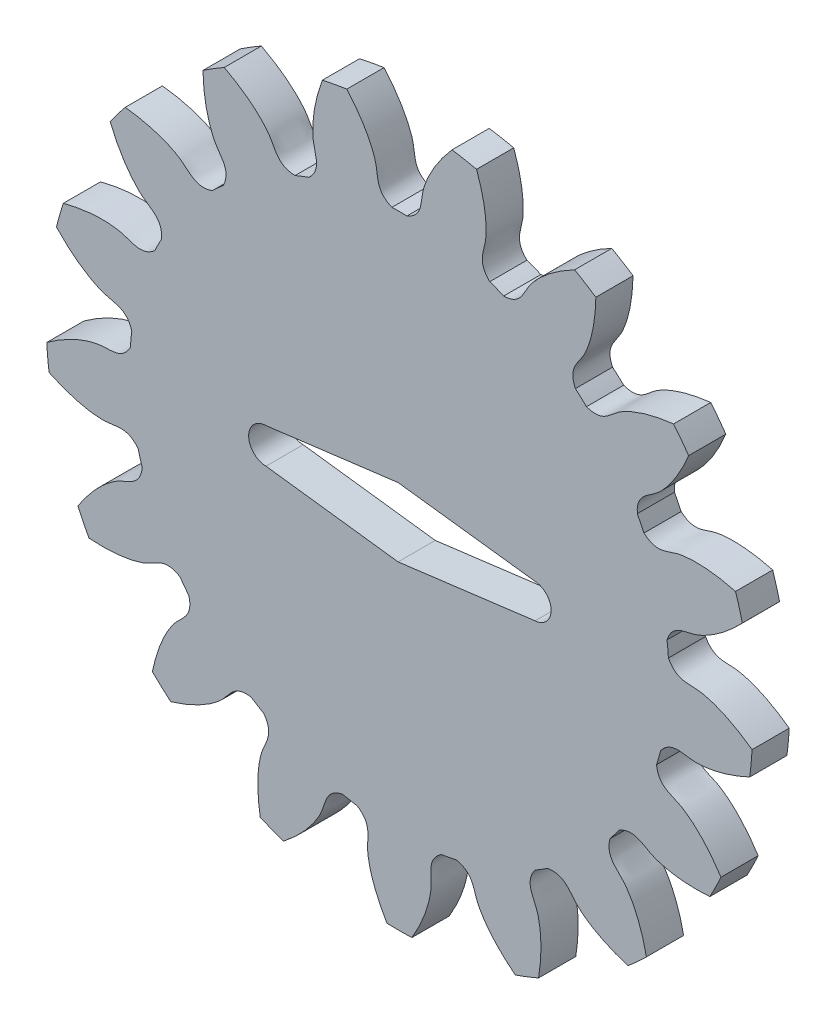
SolidWorks part; units mm, degrees
ref_plane "前视基准面" through (0, 0, 0) normal (0, 0, 1) x (1, 0, 0)
ref_plane "上视基准面" through (0, 0, 0) normal (0, 1, 0) x (1, 0, 0)
ref_plane "右视基准面" through (0, 0, 0) normal (1, 0, 0) x (0, 0, -1)
sketch "草图1" plane through (0, 0, 0) normal (0, 0, 1) x (1, 0, 0)
  circle A0 centre (0, 0) radius 38
extrude "凸台-拉伸1" add sketch "草图1" along normal blind 30
ref_axis "基准轴1" through (0, 0, -0.4001) along (0, 0, 1)
sketch "草图2" plane through (0, 0, 0) normal (0, 0, 1) x (1, 0, 0)
  line L0 (0, 0) -> (0, 38) construction
  circle A0 centre (0, 0) radius 38 construction
  arc A1 (0.8068, 28.9888) -> (-0.8068, 28.9888) centre (0, 0) ccw
  arc A2 (12.4626, 42.9629) -> (-12.4626, 42.9629) centre (0, 0) ccw
  spline S0 degree 3 poles (0.8068, 28.9888) (2.5115, 29.6993) (2.2648, 31.0193) (2.5532, 32.2593) (2.5799, 32.3646) (2.6121, 32.4817) (2.6502, 32.6103) (2.6948, 32.7504) (2.7462, 32.9016) (2.8051, 33.0638) (2.8717, 33.2367) (2.9467, 33.4201) (3.0303, 33.6137) (3.1231, 33.8172) (3.2255, 34.0303) (3.3379, 34.2527) (3.4607, 34.4842) (3.5944, 34.7243) (3.7392, 34.9727) (3.8956, 35.2291) (4.064, 35.4931) (4.2448, 35.7643) (4.4382, 36.0423) (4.6446, 36.3267) (4.8644, 36.6172) (5.0979, 36.9132) (5.3454, 37.2144) (5.6071, 37.5203) (5.8834, 37.8304) (6.1745, 38.1443) (6.4808, 38.4616) (6.8024, 38.7816) (7.1395, 39.104) (7.4925, 39.4282) (7.8614, 39.7538) (8.2465, 40.0802) (8.648, 40.4069) (9.066, 40.7334) (9.5007, 41.0591) (9.9522, 41.3835) (10.4206, 41.706) (10.906, 42.0262) (11.5833, 42.4537) (12.1063, 42.7621) (12.4626, 42.9629) knots 0 0 0 0 0.193883 0.199024 0.204851 0.211363 0.21856 0.226443 0.235011 0.244265 0.254205 0.264829 0.27614 0.288136 0.300817 0.314184 0.328236 0.342973 0.358397 0.374505 0.391299 0.408779 0.426944 0.445795 0.465331 0.485552 0.506459 0.528051 0.550329 0.573293 0.596941 0.621276 0.646296 0.672001 0.698392 0.725468 0.753229 0.781677 0.810809 0.840627 0.871131 0.90232 0.934195 1 1 1 1
  spline S1 degree 3 poles (-0.8068, 28.9888) (-2.5115, 29.6993) (-2.2648, 31.0193) (-2.5532, 32.2593) (-2.5799, 32.3646) (-2.6121, 32.4817) (-2.6502, 32.6103) (-2.6948, 32.7504) (-2.7462, 32.9016) (-2.8051, 33.0638) (-2.8717, 33.2367) (-2.9467, 33.4201) (-3.0303, 33.6137) (-3.1231, 33.8172) (-3.2255, 34.0303) (-3.3379, 34.2527) (-3.4607, 34.4842) (-3.5944, 34.7243) (-3.7392, 34.9727) (-3.8956, 35.2291) (-4.064, 35.4931) (-4.2448, 35.7643) (-4.4382, 36.0423) (-4.6446, 36.3267) (-4.8644, 36.6172) (-5.0979, 36.9132) (-5.3454, 37.2144) (-5.6071, 37.5203) (-5.8834, 37.8304) (-6.1745, 38.1443) (-6.4808, 38.4616) (-6.8024, 38.7816) (-7.1395, 39.104) (-7.4925, 39.4282) (-7.8614, 39.7538) (-8.2465, 40.0802) (-8.648, 40.4069) (-9.066, 40.7334) (-9.5007, 41.0591) (-9.9522, 41.3835) (-10.4206, 41.706) (-10.906, 42.0262) (-11.5833, 42.4537) (-12.1063, 42.7621) (-12.4626, 42.9629) knots 0 0 0 0 0.193883 0.199024 0.204851 0.211363 0.21856 0.226443 0.235011 0.244265 0.254205 0.264829 0.27614 0.288136 0.300817 0.314184 0.328236 0.342973 0.358397 0.374505 0.391299 0.408779 0.426944 0.445795 0.465331 0.485552 0.506459 0.528051 0.550329 0.573293 0.596941 0.621276 0.646296 0.672001 0.698392 0.725468 0.753229 0.781677 0.810809 0.840627 0.871131 0.90232 0.934195 1 1 1 1
extrude "切除-拉伸1" cut sketch "草图2" along normal through all
pattern_circular "阵列(圆周)1" count 17 every 21.176 about axis through (0, 0, -0.4001) along (0, 0, 1) of "切除-拉伸1"
sketch "草图3" plane through (0, 0, 0) normal (0, 0, 1) x (1, 0, 0)
  circle A0 centre (0, 0) radius 34 construction
  dimension "Dn" = 68
sketch "草图4" plane through (0, 0, 30) normal (0, 0, 1) x (1, 0, 0)
  arc A34 (-9.7197, 27.3227) -> (-11.2242, 26.7398) centre (0, 0) ccw
  arc A35 (-18.8502, 32.995) -> (-21.1337, 31.5811) centre (0, 0) ccw
  arc A36 (-18.9334, 21.9665) -> (-20.1258, 20.8794) centre (0, 0) ccw
  arc A37 (-29.4964, 23.9575) -> (-31.115, 21.8142) centre (0, 0) ccw
  arc A38 (-25.5901, 13.6436) -> (-26.3093, 12.1992) centre (0, 0) ccw
  arc A39 (-36.159, 11.6843) -> (-36.894, 9.1011) centre (0, 0) ccw
  arc A40 (-28.7907, 3.4781) -> (-28.9396, 1.8714) centre (0, 0) ccw
  arc A41 (-37.9382, -2.1669) -> (-37.6904, -4.8412) centre (0, 0) ccw
  arc A42 (-28.1029, -7.1572) -> (-27.6614, -8.7091) centre (0, 0) ccw
  arc A43 (-34.5935, -15.7254) -> (-33.3964, -18.1296) centre (0, 0) ccw
  arc A44 (-23.6197, -16.8258) -> (-22.6474, -18.1135) centre (0, 0) ccw
  arc A45 (-26.5768, -27.1601) -> (-24.592, -28.9695) centre (0, 0) ccw
  arc A46 (-15.9466, -24.222) -> (-14.5747, -25.0715) centre (0, 0) ccw
  arc A47 (-14.9708, -34.9267) -> (-12.4664, -35.8969) centre (0, 0) ccw
  arc A48 (-6.1197, -28.3469) -> (-4.5336, -28.6434) centre (0, 0) ccw
  arc A49 (-1.3429, -37.9763) -> (1.3429, -37.9763) centre (0, 0) ccw
  arc A50 (4.5336, -28.6434) -> (6.1197, -28.3469) centre (0, 0) ccw
  arc A51 (12.4664, -35.8969) -> (14.9708, -34.9267) centre (0, 0) ccw
  arc A52 (14.5747, -25.0715) -> (15.9466, -24.222) centre (0, 0) ccw
  arc A53 (24.592, -28.9695) -> (26.5768, -27.1601) centre (0, 0) ccw
  arc A54 (22.6474, -18.1135) -> (23.6197, -16.8258) centre (0, 0) ccw
  arc A55 (33.3964, -18.1296) -> (34.5935, -15.7254) centre (0, 0) ccw
  arc A56 (27.6614, -8.7091) -> (28.1029, -7.1572) centre (0, 0) ccw
  arc A57 (37.6904, -4.8412) -> (37.9382, -2.1669) centre (0, 0) ccw
  arc A58 (28.9396, 1.8714) -> (28.7907, 3.4781) centre (0, 0) ccw
  arc A59 (36.894, 9.1011) -> (36.159, 11.6843) centre (0, 0) ccw
  arc A60 (26.3093, 12.1992) -> (25.5901, 13.6436) centre (0, 0) ccw
  arc A61 (31.115, 21.8142) -> (29.4964, 23.9575) centre (0, 0) ccw
  arc A62 (20.1258, 20.8794) -> (18.9334, 21.9665) centre (0, 0) ccw
  arc A63 (21.1337, 31.5811) -> (18.8502, 32.995) centre (0, 0) ccw
  arc A64 (11.2242, 26.7398) -> (9.7197, 27.3227) centre (0, 0) ccw
  arc A65 (8.2981, 37.0829) -> (5.6581, 37.5764) centre (0, 0) ccw
  arc A66 (0.8068, 28.9888) -> (-0.8068, 28.9888) centre (0, 0) ccw
  arc A67 (-5.6581, 37.5764) -> (-8.2981, 37.0829) centre (0, 0) ccw
  arc A68 (-9.7197, 27.3227) -> (-11.2242, 26.7398) centre (0, 0) ccw
  arc A69 (-18.8502, 32.995) -> (-21.1337, 31.5811) centre (0, 0) ccw
  arc A70 (-18.9334, 21.9665) -> (-20.1258, 20.8794) centre (0, 0) ccw
  arc A71 (-29.4964, 23.9575) -> (-31.115, 21.8142) centre (0, 0) ccw
  arc A72 (-25.5901, 13.6436) -> (-26.3093, 12.1992) centre (0, 0) ccw
  arc A73 (-36.159, 11.6843) -> (-36.894, 9.1011) centre (0, 0) ccw
  arc A74 (-28.7907, 3.4781) -> (-28.9396, 1.8714) centre (0, 0) ccw
  arc A75 (-37.9382, -2.1669) -> (-37.6904, -4.8412) centre (0, 0) ccw
  arc A76 (-28.1029, -7.1572) -> (-27.6614, -8.7091) centre (0, 0) ccw
  arc A77 (-34.5935, -15.7254) -> (-33.3964, -18.1296) centre (0, 0) ccw
  arc A78 (-23.6197, -16.8258) -> (-22.6474, -18.1135) centre (0, 0) ccw
  arc A79 (-26.5768, -27.1601) -> (-24.592, -28.9695) centre (0, 0) ccw
  arc A80 (-15.9466, -24.222) -> (-14.5747, -25.0715) centre (0, 0) ccw
  arc A81 (-14.9708, -34.9267) -> (-12.4664, -35.8969) centre (0, 0) ccw
  arc A82 (-6.1197, -28.3469) -> (-4.5336, -28.6434) centre (0, 0) ccw
  arc A83 (-1.3429, -37.9763) -> (1.3429, -37.9763) centre (0, 0) ccw
  arc A84 (4.5336, -28.6434) -> (6.1197, -28.3469) centre (0, 0) ccw
  arc A85 (12.4664, -35.8969) -> (14.9708, -34.9267) centre (0, 0) ccw
  arc A86 (14.5747, -25.0715) -> (15.9466, -24.222) centre (0, 0) ccw
  arc A87 (24.592, -28.9695) -> (26.5768, -27.1601) centre (0, 0) ccw
  arc A88 (22.6474, -18.1135) -> (23.6197, -16.8258) centre (0, 0) ccw
  arc A89 (33.3964, -18.1296) -> (34.5935, -15.7254) centre (0, 0) ccw
  arc A90 (27.6614, -8.7091) -> (28.1029, -7.1572) centre (0, 0) ccw
  arc A91 (37.6904, -4.8412) -> (37.9382, -2.1669) centre (0, 0) ccw
  arc A92 (28.9396, 1.8714) -> (28.7907, 3.4781) centre (0, 0) ccw
  arc A93 (36.894, 9.1011) -> (36.159, 11.6843) centre (0, 0) ccw
  arc A94 (26.3093, 12.1992) -> (25.5901, 13.6436) centre (0, 0) ccw
  arc A95 (31.115, 21.8142) -> (29.4964, 23.9575) centre (0, 0) ccw
  arc A96 (20.1258, 20.8794) -> (18.9334, 21.9665) centre (0, 0) ccw
  arc A97 (21.1337, 31.5811) -> (18.8502, 32.995) centre (0, 0) ccw
  arc A98 (11.2242, 26.7398) -> (9.7197, 27.3227) centre (0, 0) ccw
  arc A99 (8.2981, 37.0829) -> (5.6581, 37.5764) centre (0, 0) ccw
  arc A100 (0.8068, 28.9888) -> (-0.8068, 28.9888) centre (0, 0) ccw
  arc A101 (-5.6581, 37.5764) -> (-8.2981, 37.0829) centre (0, 0) ccw
  spline S34 degree 3 poles (3206.483, 2402.1157) (-58.0397, -34.3217) (-5.9601, 17.3094) (-14.057, 29.192) (-14.1473, 29.316) (-14.2515, 29.4509) (-14.3436, 29.5654) (-14.4462, 29.6878) (-14.5597, 29.8178) (-14.6843, 29.9549) (-14.8204, 30.0989) (-14.9684, 30.2492) (-15.1284, 30.4054) (-15.3009, 30.5671) (-15.486, 30.7339) (-15.6842, 30.9054) (-15.8955, 31.081) (-16.1203, 31.2603) (-16.3588, 31.4429) (-16.6112, 31.6282) (-16.8777, 31.8158) (-17.2591, 32.0731) (-17.6627, 32.3277) (-18.2038, 32.6472) (-77.0998, 65.046) (-288.9949, -194.6821) (3590.3012, 1755.8862) knots -1.634579 -1.634579 -1.634579 -1.634579 0.661536 0.666677 0.679016 0.686213 0.694096 0.702664 0.711918 0.721858 0.732483 0.743793 0.755789 0.76847 0.781837 0.795889 0.810627 0.82605 0.842158 0.858952 0.876432 0.894597 0.932984 0.953205 0.995704 11.747144 11.747144 11.747144 11.747144 only from (-11.2242, 26.7398) to (-18.8502, 32.995)
  spline S35 degree 3 poles (-3163.825, -2442.2332) (259.4388, 165.7331) (-24.272, 92.345) (-21.0946, 30.5924) (-21.0547, 30.0997) (-21.0017, 29.6255) (-20.9573, 29.2898) (-20.9082, 28.9676) (-20.8548, 28.6591) (-20.7976, 28.3642) (-20.7373, 28.0831) (-20.6743, 27.8156) (-20.6092, 27.5618) (-20.5424, 27.3217) (-20.4745, 27.0952) (-20.406, 26.8823) (-20.3374, 26.6829) (-20.2692, 26.4969) (-20.202, 26.3242) (-20.1362, 26.1647) (-20.0723, 26.0183) (-20.0109, 25.8848) (-19.9366, 25.7314) (-19.8659, 25.5953) (-12.8382, 13.0508) (56.5937, 36.6564) (-3579.505, -1799.594) knots -9.862812 -9.862812 -9.862812 -9.862812 0.025888 0.046795 0.086552 0.105403 0.123568 0.141048 0.157842 0.17395 0.189373 0.204111 0.218163 0.23153 0.244211 0.256207 0.267517 0.278142 0.288082 0.297336 0.305904 0.313787 0.320984 0.333323 0.338464 2.634572 2.634572 2.634572 2.634572 only from (-21.1337, 31.5811) to (-18.9334, 21.9665)
  spline S36 degree 3 poles (2122.2121, 3398.2214) (-41.722, -52.9705) (-11.8105, 13.9875) (-23.6531, 22.1428) (-23.7821, 22.2258) (-23.928, 22.3139) (-24.0553, 22.3874) (-24.1952, 22.4645) (-24.3479, 22.5447) (-24.5137, 22.6276) (-24.6926, 22.7126) (-24.8848, 22.7993) (-25.0905, 22.8872) (-25.3098, 22.9757) (-25.5427, 23.0643) (-25.7894, 23.1526) (-26.0499, 23.24) (-26.3243, 23.326) (-26.6126, 23.4101) (-26.9149, 23.4918) (-27.2311, 23.5704) (-27.6798, 23.6725) (-28.1481, 23.7642) (-28.7681, 23.8666) (-95.3907, 32.802) (-199.1525, -285.9327) (2713.5569, 2934.2815) knots -1.634579 -1.634579 -1.634579 -1.634579 0.661536 0.666677 0.679016 0.686213 0.694096 0.702664 0.711918 0.721858 0.732483 0.743793 0.755789 0.76847 0.781837 0.795889 0.810627 0.82605 0.842158 0.858952 0.876432 0.894597 0.932984 0.953205 0.995704 11.747144 11.747144 11.747144 11.747144 only from (-20.1258, 20.8794) to (-29.4964, 23.9575)
  spline S37 degree 3 poles (-2067.9426, -3420.22) (182.0498, 248.2616) (-55.9918, 77.3411) (-30.7214, 20.9063) (-30.5062, 20.4613) (-30.2855, 20.0383) (-30.1228, 19.7413) (-29.9606, 19.4586) (-29.7993, 19.1902) (-29.6396, 18.9359) (-29.4817, 18.6955) (-29.3264, 18.4688) (-29.1739, 18.2558) (-29.0249, 18.056) (-28.8798, 17.8693) (-28.739, 17.6956) (-28.603, 17.5344) (-28.4723, 17.3856) (-28.3472, 17.2488) (-28.2282, 17.1239) (-28.1158, 17.0104) (-28.0103, 16.908) (-27.8856, 16.7919) (-27.7705, 16.6905) (-16.6857, 7.5318) (39.5302, 54.6251) (-2687.7007, -2971.1378) knots -9.862812 -9.862812 -9.862812 -9.862812 0.025888 0.046795 0.086552 0.105403 0.123568 0.141048 0.157842 0.17395 0.189373 0.204111 0.218163 0.23153 0.244211 0.256207 0.267517 0.278142 0.288082 0.297336 0.305904 0.313787 0.320984 0.333323 0.338464 2.634572 2.634572 2.634572 2.634572 only from (-31.115, 21.8142) to (-25.5901, 13.6436)
  spline S38 degree 3 poles (751.3247, 3935.3785) (-19.7695, -64.4652) (-16.0658, 8.7765) (-30.0548, 12.103) (-30.205, 12.1338) (-30.3729, 12.1633) (-30.5181, 12.1859) (-30.6764, 12.2072) (-30.8479, 12.2268) (-31.0324, 12.2442) (-31.2299, 12.2589) (-31.4405, 12.2703) (-31.664, 12.2779) (-31.9004, 12.2812) (-32.1496, 12.2798) (-32.4115, 12.273) (-32.686, 12.2604) (-32.973, 12.2415) (-33.2722, 12.2157) (-33.5836, 12.1826) (-33.9069, 12.1417) (-34.3621, 12.0749) (-34.8319, 11.9912) (-35.447, 11.8628) (-100.7987, -3.8722) (-82.4133, -338.5665) (1470.3316, 3716.3859) knots -1.634579 -1.634579 -1.634579 -1.634579 0.661536 0.666677 0.679016 0.686213 0.694096 0.702664 0.711918 0.721858 0.732483 0.743793 0.755789 0.76847 0.781837 0.795889 0.810627 0.82605 0.842158 0.858952 0.876432 0.894597 0.932984 0.953205 0.995704 11.747144 11.747144 11.747144 11.747144 only from (-26.3093, 12.1992) to (-36.159, 11.6843)
  spline S39 degree 3 poles (-692.7731, -3936.2872) (80.074, 297.261) (-80.1497, 51.8919) (-36.1991, 8.3967) (-35.8377, 8.0595) (-35.479, 7.7448) (-35.22, 7.5266) (-34.9667, 7.3216) (-34.7193, 7.1296) (-34.4785, 6.9501) (-34.2445, 6.783) (-34.0177, 6.6278) (-33.7986, 6.4841) (-33.5875, 6.3517) (-33.3848, 6.2301) (-33.1907, 6.1189) (-33.0057, 6.0177) (-32.83, 5.9262) (-32.664, 5.8439) (-32.5079, 5.7703) (-32.362, 5.7051) (-32.2267, 5.6478) (-32.0685, 5.5845) (-31.9245, 5.5316) (-18.2797, 0.9956) (17.128, 65.2163) (-1432.9075, -3741.4129) knots -9.862812 -9.862812 -9.862812 -9.862812 0.025888 0.046795 0.086552 0.105403 0.123568 0.141048 0.157842 0.17395 0.189373 0.204111 0.218163 0.23153 0.244211 0.256207 0.267517 0.278142 0.288082 0.297336 0.305904 0.313787 0.320984 0.333323 0.338464 2.634572 2.634572 2.634572 2.634572 only from (-36.894, 9.1011) to (-28.7907, 3.4781)
  spline S40 degree 3 poles (-721.0333, 3941.041) (4.853, -67.2536) (-18.1514, 2.3802) (-32.3974, 0.4287) (-32.5486, 0.4031) (-32.7158, 0.37) (-32.8593, 0.3386) (-33.0147, 0.3013) (-33.1816, 0.2576) (-33.3599, 0.2072) (-33.5494, 0.1495) (-33.7499, 0.0841) (-33.9611, 0.0104) (-34.1827, -0.0719) (-34.4146, -0.1633) (-34.6564, -0.2642) (-34.9078, -0.3751) (-35.1685, -0.4964) (-35.4382, -0.6285) (-35.7166, -0.7718) (-36.0033, -0.9268) (-36.4037, -1.1535) (-36.8115, -1.4013) (-37.3387, -1.7433) (-92.5932, -40.0234) (45.4562, -345.475) (28.5301, 3996.5717) knots -1.634579 -1.634579 -1.634579 -1.634579 0.661536 0.666677 0.679016 0.686213 0.694096 0.702664 0.711918 0.721858 0.732483 0.743793 0.755789 0.76847 0.781837 0.795889 0.810627 0.82605 0.842158 0.858952 0.876432 0.894597 0.932984 0.953205 0.995704 11.747144 11.747144 11.747144 11.747144 only from (-28.9396, 1.8714) to (-37.9382, -2.1669)
  spline S41 degree 3 poles (775.9593, -3920.737) (-32.7163, 306.1137) (-93.4828, 19.4343) (-36.7879, -5.247) (-36.3291, -5.4308) (-35.881, -5.5947) (-35.5606, -5.7046) (-35.2503, -5.8042) (-34.9503, -5.894) (-34.6609, -5.9743) (-34.3823, -6.0456) (-34.1148, -6.1084) (-33.8586, -6.1632) (-33.6139, -6.2104) (-33.3809, -6.2506) (-33.1598, -6.2842) (-32.9507, -6.3117) (-32.7538, -6.3336) (-32.5693, -6.3504) (-32.3972, -6.3626) (-32.2376, -6.3707) (-32.0907, -6.3752) (-31.9203, -6.3771) (-31.767, -6.3744) (-17.405, -5.675) (-7.5875, 66.9998) (15.4078, -4006.3895) knots -9.862812 -9.862812 -9.862812 -9.862812 0.025888 0.046795 0.086552 0.105403 0.123568 0.141048 0.157842 0.17395 0.189373 0.204111 0.218163 0.23153 0.244211 0.256207 0.267517 0.278142 0.288082 0.297336 0.305904 0.313787 0.320984 0.333323 0.338464 2.634572 2.634572 2.634572 2.634572 only from (-37.6904, -4.8412) to (-28.1029, -7.1572)
  spline S42 degree 3 poles (-2096.0117, 3414.444) (28.8201, -60.959) (-17.7855, -4.3375) (-30.3645, -11.3035) (-30.4963, -11.382) (-30.6402, -11.4733) (-30.7627, -11.5545) (-30.8941, -11.6454) (-31.034, -11.7463) (-31.1821, -11.8578) (-31.3379, -11.98) (-31.5012, -12.1135) (-31.6715, -12.2584) (-31.8485, -12.4152) (-32.0317, -12.5842) (-32.2207, -12.7657) (-32.415, -12.9599) (-32.6143, -13.1672) (-32.8181, -13.3878) (-33.026, -13.622) (-33.2373, -13.8701) (-33.5287, -14.2262) (-33.8195, -14.6045) (-34.1876, -15.1138) (-71.8824, -70.7692) (167.1866, -305.7251) (-1417.1247, 3736.9983) knots -1.634579 -1.634579 -1.634579 -1.634579 0.661536 0.666677 0.679016 0.686213 0.694096 0.702664 0.711918 0.721858 0.732483 0.743793 0.755789 0.76847 0.781837 0.795889 0.810627 0.82605 0.842158 0.858952 0.876432 0.894597 0.932984 0.953205 0.995704 11.747144 11.747144 11.747144 11.747144 only from (-27.6614, -8.7091) to (-34.5935, -15.7254)
  spline S43 degree 3 poles (2139.8941, -3375.6695) (-141.0881, 273.624) (-94.1906, -15.6479) (-32.4082, -18.1819) (-31.914, -18.1876) (-31.437, -18.1786) (-31.0985, -18.1654) (-30.7732, -18.1462) (-30.4611, -18.1215) (-30.1622, -18.0918) (-29.8767, -18.0577) (-29.6045, -18.0196) (-29.3458, -17.9782) (-29.1006, -17.9338) (-28.8688, -17.8871) (-28.6505, -17.8385) (-28.4456, -17.7886) (-28.2541, -17.7379) (-28.0759, -17.6869) (-27.911, -17.6361) (-27.7593, -17.5861) (-27.6207, -17.5372) (-27.4612, -17.4774) (-27.3191, -17.4195) (-14.1796, -11.5792) (-31.2782, 59.7345) (1461.6422, -3730.281) knots -9.862812 -9.862812 -9.862812 -9.862812 0.025888 0.046795 0.086552 0.105403 0.123568 0.141048 0.157842 0.17395 0.189373 0.204111 0.218163 0.23153 0.244211 0.256207 0.267517 0.278142 0.288082 0.297336 0.305904 0.313787 0.320984 0.333323 0.338464 2.634572 2.634572 2.634572 2.634572 only from (-33.3964, -18.1296) to (-23.6197, -16.8258)
  spline S44 degree 3 poles (-3187.9122, 2426.7074) (48.8949, -46.4315) (-15.0176, -10.4695) (-24.2307, -21.5092) (-24.3253, -21.6299) (-24.4265, -21.767) (-24.5114, -21.887) (-24.6011, -22.0192) (-24.6951, -22.1639) (-24.7929, -22.3213) (-24.8941, -22.4916) (-24.9981, -22.675) (-25.1046, -22.8717) (-25.2129, -23.0819) (-25.3227, -23.3056) (-25.4334, -23.5431) (-25.5445, -23.7944) (-25.6554, -24.0597) (-25.7658, -24.339) (-25.8749, -24.6325) (-25.9824, -24.9402) (-26.1255, -25.3775) (-26.26, -25.8353) (-26.4192, -26.4432) (-41.4636, -91.9572) (266.3375, -224.6854) (-2671.389, 2972.7227) knots -1.634579 -1.634579 -1.634579 -1.634579 0.661536 0.666677 0.679016 0.686213 0.694096 0.702664 0.711918 0.721858 0.732483 0.743793 0.755789 0.76847 0.781837 0.795889 0.810627 0.82605 0.842158 0.858952 0.876432 0.894597 0.932984 0.953205 0.995704 11.747144 11.747144 11.747144 11.747144 only from (-22.6474, -18.1135) to (-26.5768, -27.1601)
  spline S45 degree 3 poles (3214.8243, -2374.6992) (-230.4051, 204.1799) (-82.1775, -48.6168) (-23.6517, -28.6614) (-23.1888, -28.4881) (-22.7472, -28.3074) (-22.4364, -28.1728) (-22.14, -28.0374) (-21.8579, -27.9016) (-21.5899, -27.7659) (-21.336, -27.631) (-21.096, -27.4972) (-20.8697, -27.3651) (-20.6571, -27.2351) (-20.4578, -27.1078) (-20.2718, -26.9837) (-20.0987, -26.8631) (-19.9385, -26.7467) (-19.7908, -26.6348) (-19.6554, -26.5278) (-19.532, -26.4263) (-19.4204, -26.3307) (-19.2932, -26.2173) (-19.1817, -26.112) (-9.0392, -15.9196) (-50.7447, 44.4018) (2710.4737, -2950.3774) knots -9.862812 -9.862812 -9.862812 -9.862812 0.025888 0.046795 0.086552 0.105403 0.123568 0.141048 0.157842 0.17395 0.189373 0.204111 0.218163 0.23153 0.244211 0.256207 0.267517 0.278142 0.288082 0.297336 0.305904 0.313787 0.320984 0.333323 0.338464 2.634572 2.634572 2.634572 2.634572 only from (-24.592, -28.9695) to (-15.9466, -24.222)
  spline S46 degree 3 poles (-3849.2674, 1111.2306) (62.3661, -25.6332) (-10.2215, -15.1875) (-14.8245, -28.8098) (-14.869, -28.9566) (-14.9139, -29.121) (-14.9497, -29.2636) (-14.9856, -29.4192) (-15.0209, -29.5881) (-15.0553, -29.7702) (-15.0881, -29.9656) (-15.1189, -30.1742) (-15.1471, -30.3961) (-15.1722, -30.6312) (-15.1938, -30.8795) (-15.2112, -31.1409) (-15.224, -31.4154) (-15.2316, -31.7028) (-15.2336, -32.0032) (-15.2294, -32.3162) (-15.2185, -32.642) (-15.1939, -33.1014) (-15.1539, -33.5769) (-15.0828, -34.2013) (-5.4449, -100.726) (329.5181, -113.3007) (-3564.8673, 1806.9643) knots -1.634579 -1.634579 -1.634579 -1.634579 0.661536 0.666677 0.679016 0.686213 0.694096 0.702664 0.711918 0.721858 0.732483 0.743793 0.755789 0.76847 0.781837 0.795889 0.810627 0.82605 0.842158 0.858952 0.876432 0.894597 0.932984 0.953205 0.995704 11.747144 11.747144 11.747144 11.747144 only from (-14.5747, -25.0715) to (-14.9708, -34.9267)
  spline S47 degree 3 poles (3855.5747, -1053.0126) (-288.6047, 107.1602) (-59.0658, -75.0198) (-11.7009, -35.2699) (-11.3318, -34.9412) (-10.9854, -34.6131) (-10.7442, -34.3753) (-10.5167, -34.142) (-10.3026, -33.9134) (-10.1018, -33.6901) (-9.9137, -33.4726) (-9.7383, -33.2611) (-9.575, -33.0562) (-9.4237, -32.8582) (-9.2839, -32.6675) (-9.1552, -32.4845) (-9.0374, -32.3096) (-8.9301, -32.1431) (-8.8328, -31.9854) (-8.7451, -31.8368) (-8.6668, -31.6976) (-8.5972, -31.5681) (-8.5196, -31.4164) (-8.4536, -31.2779) (-2.678, -18.1099) (-63.3577, 23.0723) (3593.2407, -1772.009) knots -9.862812 -9.862812 -9.862812 -9.862812 0.025888 0.046795 0.086552 0.105403 0.123568 0.141048 0.157842 0.17395 0.189373 0.204111 0.218163 0.23153 0.244211 0.256207 0.267517 0.278142 0.288082 0.297336 0.305904 0.313787 0.320984 0.333323 0.338464 2.634572 2.634572 2.634572 2.634572 only from (-12.4664, -35.8969) to (-6.1197, -28.3469)
  spline S48 degree 3 poles (-3990.7577, -354.3241) (67.4145, -1.373) (-4.0449, -17.8544) (-3.4161, -32.2196) (-3.4046, -32.3726) (-3.3871, -32.5421) (-3.369, -32.6879) (-3.3462, -32.846) (-3.3182, -33.0163) (-3.2844, -33.1985) (-3.2444, -33.3925) (-3.1978, -33.5982) (-3.1439, -33.8153) (-3.0824, -34.0436) (-3.0128, -34.2829) (-2.9346, -34.5329) (-2.8474, -34.7935) (-2.7507, -35.0643) (-2.644, -35.3451) (-2.527, -35.6355) (-2.3992, -35.9353) (-2.2103, -36.3548) (-2.0012, -36.7838) (-1.7094, -37.3403) (31.3092, -95.8911) (348.1954, 13.3859) (-3976.8906, 397.1654) knots -1.634579 -1.634579 -1.634579 -1.634579 0.661536 0.666677 0.679016 0.686213 0.694096 0.702664 0.711918 0.721858 0.732483 0.743793 0.755789 0.76847 0.781837 0.795889 0.810627 0.82605 0.842158 0.858952 0.876432 0.894597 0.932984 0.953205 0.995704 11.747144 11.747144 11.747144 11.747144 only from (-4.5336, -28.6434) to (-1.3429, -37.9763)
  spline S49 degree 3 poles (3975.6083, 410.8892) (-307.8266, -4.3321) (-27.9769, -91.2909) (1.8302, -37.115) (2.0556, -36.6752) (2.2601, -36.2441) (2.3992, -35.9353) (2.527, -35.6355) (2.644, -35.3451) (2.7507, -35.0643) (2.8474, -34.7935) (2.9346, -34.5329) (3.0128, -34.2829) (3.0824, -34.0436) (3.1439, -33.8153) (3.1978, -33.5982) (3.2444, -33.3925) (3.2844, -33.1985) (3.3182, -33.0163) (3.3462, -32.846) (3.369, -32.6879) (3.3871, -32.5421) (3.4046, -32.3726) (3.4161, -32.2196) (4.0449, -17.8544) (-67.414, -1.3731) (3990.7206, -354.3209) knots -9.862812 -9.862812 -9.862812 -9.862812 0.025888 0.046795 0.086552 0.105403 0.123568 0.141048 0.157842 0.17395 0.189373 0.204111 0.218163 0.23153 0.244211 0.256207 0.267517 0.278142 0.288082 0.297336 0.305904 0.313787 0.320984 0.333323 0.338464 2.634572 2.634572 2.634572 2.634572 only from (1.3429, -37.9763) to (4.5336, -28.6434)
  spline S50 degree 3 poles (-3593.2741, -1772.0254) (63.3581, 23.0726) (2.678, -18.1099) (8.4536, -31.2779) (8.5196, -31.4164) (8.5972, -31.5681) (8.6668, -31.6976) (8.7451, -31.8368) (8.8328, -31.9854) (8.9301, -32.1431) (9.0374, -32.3096) (9.1552, -32.4845) (9.2839, -32.6675) (9.4237, -32.8582) (9.575, -33.0562) (9.7383, -33.2611) (9.9137, -33.4726) (10.1018, -33.6901) (10.3026, -33.9134) (10.5167, -34.142) (10.7442, -34.3753) (11.0718, -34.6983) (11.4218, -35.0228) (11.8949, -35.4363) (63.8348, -78.1056) (319.847, 138.2646) (-3851.8127, -1066.2729) knots -1.634579 -1.634579 -1.634579 -1.634579 0.661536 0.666677 0.679016 0.686213 0.694096 0.702664 0.711918 0.721858 0.732483 0.743793 0.755789 0.76847 0.781837 0.795889 0.810627 0.82605 0.842158 0.858952 0.876432 0.894597 0.932984 0.953205 0.995704 11.747144 11.747144 11.747144 11.747144 only from (6.1197, -28.3469) to (12.4664, -35.8969)
  spline S51 degree 3 poles (3558.714, 1819.2982) (-285.4748, -115.2394) (6.8904, -95.2326) (15.1141, -33.9476) (15.1654, -33.456) (15.2004, -32.9802) (15.2185, -32.642) (15.2294, -32.3162) (15.2336, -32.0032) (15.2316, -31.7028) (15.224, -31.4154) (15.2112, -31.1409) (15.1938, -30.8795) (15.1722, -30.6312) (15.1471, -30.3961) (15.1189, -30.1742) (15.0881, -29.9656) (15.0553, -29.7702) (15.0209, -29.5881) (14.9856, -29.4192) (14.9497, -29.2636) (14.9139, -29.121) (14.869, -28.9566) (14.8245, -28.8098) (10.2215, -15.1875) (-62.3657, -25.6332) (3849.2316, 1111.2202) knots -9.862812 -9.862812 -9.862812 -9.862812 0.025888 0.046795 0.086552 0.105403 0.123568 0.141048 0.157842 0.17395 0.189373 0.204111 0.218163 0.23153 0.244211 0.256207 0.267517 0.278142 0.288082 0.297336 0.305904 0.313787 0.320984 0.333323 0.338464 2.634572 2.634572 2.634572 2.634572 only from (14.9708, -34.9267) to (14.5747, -25.0715)
  spline S52 degree 3 poles (-2710.4989, -2950.4048) (50.7449, 44.4021) (9.0392, -15.9195) (19.1817, -26.112) (19.2932, -26.2173) (19.4204, -26.3307) (19.532, -26.4263) (19.6554, -26.5278) (19.7908, -26.6348) (19.9385, -26.7467) (20.0987, -26.8631) (20.2718, -26.9837) (20.4578, -27.1078) (20.6571, -27.2351) (20.8697, -27.3651) (21.096, -27.4972) (21.336, -27.631) (21.5899, -27.7659) (21.8579, -27.9016) (22.14, -28.0374) (22.4364, -28.1728) (22.8587, -28.3556) (23.3022, -28.5317) (23.8927, -28.7464) (87.7392, -49.7715) (248.3015, 244.47) (-3206.5263, -2385.7051) knots -1.634579 -1.634579 -1.634579 -1.634579 0.661536 0.666677 0.679016 0.686213 0.694096 0.702664 0.711918 0.721858 0.732483 0.743793 0.755789 0.76847 0.781837 0.795889 0.810627 0.82605 0.842158 0.858952 0.876432 0.894597 0.932984 0.953205 0.995704 11.747144 11.747144 11.747144 11.747144 only from (15.9466, -24.222) to (24.592, -28.9695)
  spline S53 degree 3 poles (2661.1957, 2982.0008) (-224.568, -210.5829) (40.8271, -86.3127) (26.3568, -26.1953) (26.227, -25.7184) (26.0878, -25.2621) (25.9824, -24.9402) (25.8749, -24.6325) (25.7658, -24.339) (25.6554, -24.0597) (25.5445, -23.7944) (25.4334, -23.5431) (25.3227, -23.3056) (25.2129, -23.0819) (25.1046, -22.8717) (24.9981, -22.675) (24.8941, -22.4916) (24.7929, -22.3213) (24.6951, -22.1639) (24.6011, -22.0192) (24.5114, -21.887) (24.4265, -21.767) (24.3253, -21.6299) (24.2307, -21.5092) (15.0176, -10.4695) (-48.8945, -46.4313) (3187.8826, 2426.6848) knots -9.862812 -9.862812 -9.862812 -9.862812 0.025888 0.046795 0.086552 0.105403 0.123568 0.141048 0.157842 0.17395 0.189373 0.204111 0.218163 0.23153 0.244211 0.256207 0.267517 0.278142 0.288082 0.297336 0.305904 0.313787 0.320984 0.333323 0.338464 2.634572 2.634572 2.634572 2.634572 only from (26.5768, -27.1601) to (22.6474, -18.1135)
  spline S54 degree 3 poles (-1461.6558, -3730.3157) (31.2783, 59.7349) (14.1796, -11.5792) (27.3191, -17.4195) (27.4612, -17.4774) (27.6207, -17.5372) (27.7593, -17.5861) (27.911, -17.6361) (28.0759, -17.6869) (28.2541, -17.7379) (28.4456, -17.7886) (28.6505, -17.8385) (28.8688, -17.8871) (29.1006, -17.9338) (29.3458, -17.9782) (29.6045, -18.0196) (29.8767, -18.0577) (30.1622, -18.0918) (30.4611, -18.1215) (30.7732, -18.1462) (31.0985, -18.1654) (31.5583, -18.1833) (32.0355, -18.1873) (32.6637, -18.1742) (99.7939, -14.7155) (143.2215, 317.6583) (-2128.1805, -3382.9346) knots -1.634579 -1.634579 -1.634579 -1.634579 0.661536 0.666677 0.679016 0.686213 0.694096 0.702664 0.711918 0.721858 0.732483 0.743793 0.755789 0.76847 0.781837 0.795889 0.810627 0.82605 0.842158 0.858952 0.876432 0.894597 0.932984 0.953205 0.995704 11.747144 11.747144 11.747144 11.747144 only from (23.6197, -16.8258) to (33.3964, -18.1296)
  spline S55 degree 3 poles (1404.2682, 3741.9677) (-133.3321, -277.486) (69.2498, -65.7358) (34.0398, -14.9053) (33.7465, -14.5074) (33.4518, -14.1322) (33.2373, -13.8701) (33.026, -13.622) (32.8181, -13.3878) (32.6143, -13.1672) (32.415, -12.9599) (32.2207, -12.7657) (32.0317, -12.5842) (31.8485, -12.4152) (31.6715, -12.2584) (31.5012, -12.1135) (31.3379, -11.98) (31.1821, -11.8578) (31.034, -11.7463) (30.8941, -11.6454) (30.7627, -11.5545) (30.6402, -11.4733) (30.4963, -11.382) (30.3645, -11.3035) (17.7856, -4.3376) (-28.8198, -60.9586) (2095.9923, 3414.4122) knots -9.862812 -9.862812 -9.862812 -9.862812 0.025888 0.046795 0.086552 0.105403 0.123568 0.141048 0.157842 0.17395 0.189373 0.204111 0.218163 0.23153 0.244211 0.256207 0.267517 0.278142 0.288082 0.297336 0.305904 0.313787 0.320984 0.333323 0.338464 2.634572 2.634572 2.634572 2.634572 only from (34.5935, -15.7254) to (27.6614, -8.7091)
  spline S56 degree 3 poles (-15.408, -4006.4268) (7.5874, 67.0002) (17.405, -5.675) (31.767, -6.3744) (31.9203, -6.3771) (32.0907, -6.3752) (32.2376, -6.3707) (32.3972, -6.3626) (32.5693, -6.3504) (32.7538, -6.3336) (32.9507, -6.3117) (33.1598, -6.2842) (33.3809, -6.2506) (33.6139, -6.2104) (33.8586, -6.1632) (34.1148, -6.1084) (34.3823, -6.0456) (34.6609, -5.9743) (34.9503, -5.894) (35.2503, -5.8042) (35.5606, -5.7046) (35.9958, -5.5553) (36.4422, -5.3866) (37.0233, -5.1474) (98.3709, 22.3279) (18.7987, 347.9451) (-762.4124, -3923.2801) knots -1.634579 -1.634579 -1.634579 -1.634579 0.661536 0.666677 0.679016 0.686213 0.694096 0.702664 0.711918 0.721858 0.732483 0.743793 0.755789 0.76847 0.781837 0.795889 0.810627 0.82605 0.842158 0.858952 0.876432 0.894597 0.932984 0.953205 0.995704 11.747144 11.747144 11.747144 11.747144 only from (28.1029, -7.1572) to (37.6904, -4.8412)
  spline S57 degree 3 poles (-42.3136, 3996.5611) (-24.089, -306.9131) (88.3201, -36.2808) (37.1256, -1.6021) (36.7084, -1.3371) (36.298, -1.0937) (36.0033, -0.9268) (35.7166, -0.7718) (35.4382, -0.6285) (35.1685, -0.4964) (34.9078, -0.3751) (34.6564, -0.2642) (34.4146, -0.1633) (34.1827, -0.0719) (33.9611, 0.0104) (33.7499, 0.0841) (33.5494, 0.1495) (33.3599, 0.2072) (33.1816, 0.2576) (33.0147, 0.3013) (32.8593, 0.3386) (32.7158, 0.37) (32.5486, 0.4031) (32.3974, 0.4287) (18.1514, 2.3802) (-4.8529, -67.2531) (721.0267, 3941.0043) knots -9.862812 -9.862812 -9.862812 -9.862812 0.025888 0.046795 0.086552 0.105403 0.123568 0.141048 0.157842 0.17395 0.189373 0.204111 0.218163 0.23153 0.244211 0.256207 0.267517 0.278142 0.288082 0.297336 0.305904 0.313787 0.320984 0.333323 0.338464 2.634572 2.634572 2.634572 2.634572 only from (37.9382, -2.1669) to (28.9396, 1.8714)
  spline S58 degree 3 poles (1432.9207, -3741.4477) (-17.1282, 65.2167) (18.2797, 0.9956) (31.9245, 5.5316) (32.0685, 5.5845) (32.2267, 5.6478) (32.362, 5.7051) (32.5079, 5.7703) (32.664, 5.8439) (32.83, 5.9262) (33.0057, 6.0177) (33.1907, 6.1189) (33.3848, 6.2301) (33.5875, 6.3517) (33.7986, 6.4841) (34.0177, 6.6278) (34.2445, 6.783) (34.4785, 6.9501) (34.7193, 7.1296) (34.9667, 7.3216) (35.22, 7.5266) (35.5719, 7.823) (35.9272, 8.1415) (36.3826, 8.5745) (83.6623, 56.3558) (-108.1631, 331.24) (706.3238, -3933.7648) knots -1.634579 -1.634579 -1.634579 -1.634579 0.661536 0.666677 0.679016 0.686213 0.694096 0.702664 0.711918 0.721858 0.732483 0.743793 0.755789 0.76847 0.781837 0.795889 0.810627 0.82605 0.842158 0.858952 0.876432 0.894597 0.932984 0.953205 0.995704 11.747144 11.747144 11.747144 11.747144 only from (28.7907, 3.4781) to (36.894, 9.1011)
  spline S59 degree 3 poles (-1483.1807, 3711.3968) (88.4075, -294.8899) (95.4621, -1.926) (35.1973, 11.9174) (34.7126, 12.0138) (34.242, 12.0925) (33.9069, 12.1417) (33.5836, 12.1826) (33.2722, 12.2157) (32.973, 12.2415) (32.686, 12.2604) (32.4115, 12.273) (32.1496, 12.2798) (31.9004, 12.2812) (31.664, 12.2779) (31.4405, 12.2703) (31.2299, 12.2589) (31.0324, 12.2442) (30.8479, 12.2268) (30.6764, 12.2072) (30.5181, 12.1859) (30.3729, 12.1633) (30.205, 12.1338) (30.0548, 12.103) (16.0659, 8.7766) (19.7695, -64.4648) (-751.3176, 3935.342) knots -9.862812 -9.862812 -9.862812 -9.862812 0.025888 0.046795 0.086552 0.105403 0.123568 0.141048 0.157842 0.17395 0.189373 0.204111 0.218163 0.23153 0.244211 0.256207 0.267517 0.278142 0.288082 0.297336 0.305904 0.313787 0.320984 0.333323 0.338464 2.634572 2.634572 2.634572 2.634572 only from (36.159, 11.6843) to (26.3093, 12.1992)
  spline S60 degree 3 poles (2687.7256, -2971.1654) (-39.5306, 54.6253) (16.6857, 7.5318) (27.7705, 16.6905) (27.8856, 16.7919) (28.0103, 16.908) (28.1158, 17.0104) (28.2282, 17.1239) (28.3472, 17.2488) (28.4723, 17.3856) (28.603, 17.5344) (28.739, 17.6956) (28.8798, 17.8693) (29.0249, 18.056) (29.1739, 18.2558) (29.3264, 18.4688) (29.4817, 18.6955) (29.6396, 18.9359) (29.7993, 19.1902) (29.9606, 19.4586) (30.1228, 19.7413) (30.3438, 20.1448) (30.5601, 20.5702) (30.8283, 21.1384) (57.6547, 82.7726) (-220.5167, 269.7991) (2079.6672, -3412.9729) knots -1.634579 -1.634579 -1.634579 -1.634579 0.661536 0.666677 0.679016 0.686213 0.694096 0.702664 0.711918 0.721858 0.732483 0.743793 0.755789 0.76847 0.781837 0.795889 0.810627 0.82605 0.842158 0.858952 0.876432 0.894597 0.932984 0.953205 0.995704 11.747144 11.747144 11.747144 11.747144 only from (25.5901, 13.6436) to (31.115, 21.8142)
  spline S61 degree 3 poles (-2723.736, 2924.9878) (188.9641, -243.0402) (89.7115, 32.689) (28.5155, 23.8274) (28.0286, 23.7421) (27.5614, 23.6456) (27.2311, 23.5704) (26.9149, 23.4918) (26.6126, 23.4101) (26.3243, 23.326) (26.0499, 23.24) (25.7894, 23.1526) (25.5427, 23.0643) (25.3098, 22.9757) (25.0905, 22.8872) (24.8848, 22.7993) (24.6926, 22.7126) (24.5137, 22.6276) (24.3479, 22.5447) (24.1952, 22.4645) (24.0553, 22.3874) (23.928, 22.3139) (23.7821, 22.2258) (23.6531, 22.1428) (11.8105, 13.9876) (41.7218, -52.97) (-2122.1923, 3398.1899) knots -9.862812 -9.862812 -9.862812 -9.862812 0.025888 0.046795 0.086552 0.105403 0.123568 0.141048 0.157842 0.17395 0.189373 0.204111 0.218163 0.23153 0.244211 0.256207 0.267517 0.278142 0.288082 0.297336 0.305904 0.313787 0.320984 0.333323 0.338464 2.634572 2.634572 2.634572 2.634572 only from (29.4964, 23.9575) to (20.1258, 20.8794)
  spline S62 degree 3 poles (3579.5382, -1799.6108) (-56.5941, 36.6565) (12.8381, 13.0507) (19.8659, 25.5953) (19.9366, 25.7314) (20.0109, 25.8848) (20.0723, 26.0183) (20.1362, 26.1647) (20.202, 26.3242) (20.2692, 26.4969) (20.3374, 26.6829) (20.406, 26.8823) (20.4745, 27.0952) (20.5424, 27.3217) (20.6092, 27.5618) (20.6743, 27.8156) (20.7373, 28.0831) (20.7976, 28.3642) (20.8548, 28.6591) (20.9082, 28.9676) (20.9573, 29.2898) (21.0176, 29.7459) (21.0656, 30.2207) (21.1105, 30.8475) (23.8605, 98.0104) (-303.0884, 171.9204) (3172.1399, -2431.24) knots -1.634579 -1.634579 -1.634579 -1.634579 0.661536 0.666677 0.679016 0.686213 0.694096 0.702664 0.711918 0.721858 0.732483 0.743793 0.755789 0.76847 0.781837 0.795889 0.810627 0.82605 0.842158 0.858952 0.876432 0.894597 0.932984 0.953205 0.995704 11.747144 11.747144 11.747144 11.747144 only from (18.9334, 21.9665) to (21.1337, 31.5811)
  spline S63 degree 3 poles (-3596.4356, 1743.543) (264, -158.3665) (71.8449, 62.8891) (17.9825, 32.5193) (17.5593, 32.264) (17.1585, 32.0052) (16.8777, 31.8158) (16.6112, 31.6282) (16.3588, 31.4429) (16.1203, 31.2603) (15.8955, 31.081) (15.6842, 30.9054) (15.486, 30.7339) (15.3009, 30.5671) (15.1284, 30.4054) (14.9684, 30.2492) (14.8204, 30.0989) (14.6843, 29.9549) (14.5597, 29.8178) (14.4462, 29.6878) (14.3436, 29.5654) (14.2515, 29.4509) (14.1473, 29.316) (14.057, 29.192) (5.9601, 17.3095) (58.0394, -34.3214) (-3206.4532, 2402.0934) knots -9.862812 -9.862812 -9.862812 -9.862812 0.025888 0.046795 0.086552 0.105403 0.123568 0.141048 0.157842 0.17395 0.189373 0.204111 0.218163 0.23153 0.244211 0.256207 0.267517 0.278142 0.288082 0.297336 0.305904 0.313787 0.320984 0.333323 0.338464 2.634572 2.634572 2.634572 2.634572 only from (18.8502, 32.995) to (11.2242, 26.7398)
  spline S64 degree 3 poles (3987.9144, -385.0087) (-66.0143, 13.737) (7.2567, 16.8071) (9.2783, 31.0433) (9.2951, 31.1958) (9.309, 31.3656) (9.318, 31.5123) (9.3247, 31.6719) (9.3284, 31.8444) (9.3287, 32.0297) (9.325, 32.2278) (9.317, 32.4385) (9.3039, 32.6618) (9.2854, 32.8975) (9.261, 33.1455) (9.2301, 33.4057) (9.1922, 33.6778) (9.1469, 33.9618) (9.0936, 34.2574) (9.032, 34.5644) (8.9614, 34.8826) (8.8528, 35.3297) (8.7261, 35.7897) (8.5415, 36.3904) (-13.1562, 100.0114) (-344.7263, 50.8228) (3836.1975, -1121.1546) knots -1.634579 -1.634579 -1.634579 -1.634579 0.661536 0.666677 0.679016 0.686213 0.694096 0.702664 0.711918 0.721858 0.732483 0.743793 0.755789 0.76847 0.781837 0.795889 0.810627 0.82605 0.842158 0.858952 0.876432 0.894597 0.932984 0.953205 0.995704 11.747144 11.747144 11.747144 11.747144 only from (9.7197, 27.3227) to (8.2981, 37.0829)
  spline S65 degree 3 poles (-3983.4167, 326.623) (303.3813, -52.3046) (44.2752, 84.5957) (5.0208, 36.8194) (4.7184, 36.4284) (4.4382, 36.0423) (4.2448, 35.7643) (4.064, 35.4931) (3.8956, 35.2291) (3.7392, 34.9727) (3.5944, 34.7243) (3.4607, 34.4842) (3.3379, 34.2527) (3.2255, 34.0303) (3.1231, 33.8172) (3.0303, 33.6137) (2.9467, 33.4201) (2.8717, 33.2367) (2.8051, 33.0638) (2.7462, 32.9016) (2.6948, 32.7504) (2.6502, 32.6103) (2.6018, 32.447) (2.5624, 32.2987) (-0.6953, 18.2936) (66.5185, -11.0375) (-3857.6647, 1081.5809) knots -9.862812 -9.862812 -9.862812 -9.862812 0.025888 0.046795 0.086552 0.105403 0.123568 0.141048 0.157842 0.17395 0.189373 0.204111 0.218163 0.23153 0.244211 0.256207 0.267517 0.278142 0.288082 0.297336 0.305904 0.313787 0.320984 0.333323 0.338464 2.634572 2.634572 2.634572 2.634572 only from (5.6581, 37.5764) to (0.8068, 28.9888)
  spline S66 degree 3 poles (3857.7006, 1081.5909) (-66.5189, -11.0377) (0.6953, 18.2936) (-2.5624, 32.2987) (-2.6018, 32.447) (-2.6502, 32.6103) (-2.6948, 32.7504) (-2.7462, 32.9016) (-2.8051, 33.0638) (-2.8717, 33.2367) (-2.9467, 33.4201) (-3.0303, 33.6137) (-3.1231, 33.8172) (-3.2255, 34.0303) (-3.3379, 34.2527) (-3.4607, 34.4842) (-3.5944, 34.7243) (-3.7392, 34.9727) (-3.8956, 35.2291) (-4.064, 35.4931) (-4.2448, 35.7643) (-4.5075, 36.1419) (-4.7919, 36.5252) (-5.181, 37.0186) (-48.3961, 88.5053) (-339.8071, -77.1387) (3982.1554, 340.3488) knots -1.634579 -1.634579 -1.634579 -1.634579 0.661536 0.666677 0.679016 0.686213 0.694096 0.702664 0.711918 0.721858 0.732483 0.743793 0.755789 0.76847 0.781837 0.795889 0.810627 0.82605 0.842158 0.858952 0.876432 0.894597 0.932984 0.953205 0.995704 11.747144 11.747144 11.747144 11.747144 only from (-0.8068, 28.9888) to (-5.6581, 37.5764)
  spline S67 degree 3 poles (-3832.4153, -1134.4092) (301.7892, 60.8214) (10.7259, 94.8772) (-8.6189, 36.1468) (-8.7597, 35.673) (-8.8815, 35.2117) (-8.9614, 34.8826) (-9.032, 34.5644) (-9.0936, 34.2574) (-9.1469, 33.9618) (-9.1922, 33.6778) (-9.2301, 33.4057) (-9.261, 33.1455) (-9.2854, 32.8975) (-9.3039, 32.6618) (-9.317, 32.4385) (-9.325, 32.2278) (-9.3287, 32.0297) (-9.3284, 31.8444) (-9.3247, 31.6719) (-9.318, 31.5123) (-9.309, 31.3656) (-9.2951, 31.1958) (-9.2783, 31.0433) (-7.2567, 16.8071) (66.0139, 13.7371) (-3987.8773, -385.0051) knots -9.862812 -9.862812 -9.862812 -9.862812 0.025888 0.046795 0.086552 0.105403 0.123568 0.141048 0.157842 0.17395 0.189373 0.204111 0.218163 0.23153 0.244211 0.256207 0.267517 0.278142 0.288082 0.297336 0.305904 0.313787 0.320984 0.333323 0.338464 2.634572 2.634572 2.634572 2.634572 only from (-8.2981, 37.0829) to (-9.7197, 27.3227)
  spline S68 degree 3 poles (-11.2242, 26.7398) (-13.0705, 26.7865) (-13.3173, 28.1065) (-14.057, 29.192) (-14.1473, 29.316) (-14.2515, 29.4509) (-14.3436, 29.5654) (-14.4462, 29.6878) (-14.5597, 29.8178) (-14.6843, 29.9549) (-14.8204, 30.0989) (-14.9684, 30.2492) (-15.1284, 30.4054) (-15.3009, 30.5671) (-15.486, 30.7339) (-15.6842, 30.9054) (-15.8955, 31.081) (-16.1203, 31.2603) (-16.3588, 31.4429) (-16.6112, 31.6282) (-16.8777, 31.8158) (-17.2591, 32.0731) (-17.6627, 32.3277) (-18.2038, 32.6472) (-18.5688, 32.848) (-18.8265, 32.9827) (-18.8502, 32.995) knots 0.467653 0.467653 0.467653 0.467653 0.661536 0.666677 0.679016 0.686213 0.694096 0.702664 0.711918 0.721858 0.732483 0.743793 0.755789 0.76847 0.781837 0.795889 0.810627 0.82605 0.842158 0.858952 0.876432 0.894597 0.932984 0.953205 0.995704 1 1 1 1
  spline S69 degree 3 poles (-21.1337, 31.5811) (-21.1308, 31.4203) (-21.1223, 31.1296) (-21.0946, 30.5924) (-21.0547, 30.0997) (-21.0017, 29.6255) (-20.9573, 29.2898) (-20.9082, 28.9676) (-20.8548, 28.6591) (-20.7976, 28.3642) (-20.7373, 28.0831) (-20.6743, 27.8156) (-20.6092, 27.5618) (-20.5424, 27.3217) (-20.4745, 27.0952) (-20.406, 26.8823) (-20.3374, 26.6829) (-20.2692, 26.4969) (-20.202, 26.3242) (-20.1362, 26.1647) (-20.0723, 26.0183) (-20.0109, 25.8848) (-19.9366, 25.7314) (-19.8659, 25.5953) (-19.2238, 24.4493) (-18.1522, 23.64) (-18.9334, 21.9665) knots 0 0 0 0 0.025888 0.046795 0.086552 0.105403 0.123568 0.141048 0.157842 0.17395 0.189373 0.204111 0.218163 0.23153 0.244211 0.256207 0.267517 0.278142 0.288082 0.297336 0.305904 0.313787 0.320984 0.333323 0.338464 0.532347 0.532347 0.532347 0.532347
  spline S70 degree 3 poles (-20.1258, 20.8794) (-21.8643, 20.256) (-22.5712, 21.3977) (-23.6531, 22.1428) (-23.7821, 22.2258) (-23.928, 22.3139) (-24.0553, 22.3874) (-24.1952, 22.4645) (-24.3479, 22.5447) (-24.5137, 22.6276) (-24.6926, 22.7126) (-24.8848, 22.7993) (-25.0905, 22.8872) (-25.3098, 22.9757) (-25.5427, 23.0643) (-25.7894, 23.1526) (-26.0499, 23.24) (-26.3243, 23.326) (-26.6126, 23.4101) (-26.9149, 23.4918) (-27.2311, 23.5704) (-27.6798, 23.6725) (-28.1481, 23.7642) (-28.7681, 23.8666) (-29.1809, 23.922) (-29.4699, 23.9545) (-29.4964, 23.9575) knots 0.467653 0.467653 0.467653 0.467653 0.661536 0.666677 0.679016 0.686213 0.694096 0.702664 0.711918 0.721858 0.732483 0.743793 0.755789 0.76847 0.781837 0.795889 0.810627 0.82605 0.842158 0.858952 0.876432 0.894597 0.932984 0.953205 0.995704 1 1 1 1
  spline S71 degree 3 poles (-31.115, 21.8142) (-31.0542, 21.6652) (-30.9412, 21.3972) (-30.7214, 20.9063) (-30.5062, 20.4613) (-30.2855, 20.0383) (-30.1228, 19.7413) (-29.9606, 19.4586) (-29.7993, 19.1902) (-29.6396, 18.9359) (-29.4817, 18.6955) (-29.3264, 18.4688) (-29.1739, 18.2558) (-29.0249, 18.056) (-28.8798, 17.8693) (-28.739, 17.6956) (-28.603, 17.5344) (-28.4723, 17.3856) (-28.3472, 17.2488) (-28.2282, 17.1239) (-28.1158, 17.0104) (-28.0103, 16.908) (-27.8856, 16.7919) (-27.7705, 16.6905) (-26.7578, 15.8538) (-25.4662, 15.4863) (-25.5901, 13.6436) knots 0 0 0 0 0.025888 0.046795 0.086552 0.105403 0.123568 0.141048 0.157842 0.17395 0.189373 0.204111 0.218163 0.23153 0.244211 0.256207 0.267517 0.278142 0.288082 0.297336 0.305904 0.313787 0.320984 0.333323 0.338464 0.532347 0.532347 0.532347 0.532347
  spline S72 degree 3 poles (-26.3093, 12.1992) (-27.7052, 10.9899) (-28.7768, 11.7991) (-30.0548, 12.103) (-30.205, 12.1338) (-30.3729, 12.1633) (-30.5181, 12.1859) (-30.6764, 12.2072) (-30.8479, 12.2268) (-31.0324, 12.2442) (-31.2299, 12.2589) (-31.4405, 12.2703) (-31.664, 12.2779) (-31.9004, 12.2812) (-32.1496, 12.2798) (-32.4115, 12.273) (-32.686, 12.2604) (-32.973, 12.2415) (-33.2722, 12.2157) (-33.5836, 12.1826) (-33.9069, 12.1417) (-34.3621, 12.0749) (-34.8319, 11.9912) (-35.447, 11.8628) (-35.852, 11.7653) (-36.1332, 11.6912) (-36.159, 11.6843) knots 0.467653 0.467653 0.467653 0.467653 0.661536 0.666677 0.679016 0.686213 0.694096 0.702664 0.711918 0.721858 0.732483 0.743793 0.755789 0.76847 0.781837 0.795889 0.810627 0.82605 0.842158 0.858952 0.876432 0.894597 0.932984 0.953205 0.995704 1 1 1 1
  spline S73 degree 3 poles (-36.894, 9.1011) (-36.7836, 8.9841) (-36.5814, 8.775) (-36.1991, 8.3967) (-35.8377, 8.0595) (-35.479, 7.7448) (-35.22, 7.5266) (-34.9667, 7.3216) (-34.7193, 7.1296) (-34.4785, 6.9501) (-34.2445, 6.783) (-34.0177, 6.6278) (-33.7986, 6.4841) (-33.5875, 6.3517) (-33.3848, 6.2301) (-33.1907, 6.1189) (-33.0057, 6.0177) (-32.83, 5.9262) (-32.664, 5.8439) (-32.5079, 5.7703) (-32.362, 5.7051) (-32.2267, 5.6478) (-32.0685, 5.5845) (-31.9245, 5.5316) (-30.678, 5.1172) (-29.3409, 5.2411) (-28.7907, 3.4781) knots 0 0 0 0 0.025888 0.046795 0.086552 0.105403 0.123568 0.141048 0.157842 0.17395 0.189373 0.204111 0.218163 0.23153 0.244211 0.256207 0.267517 0.278142 0.288082 0.297336 0.305904 0.313787 0.320984 0.333323 0.338464 0.532347 0.532347 0.532347 0.532347
  spline S74 degree 3 poles (-28.9396, 1.8714) (-29.8043, 0.2395) (-31.0959, 0.607) (-32.3974, 0.4287) (-32.5486, 0.4031) (-32.7158, 0.37) (-32.8593, 0.3386) (-33.0147, 0.3013) (-33.1816, 0.2576) (-33.3599, 0.2072) (-33.5494, 0.1495) (-33.7499, 0.0841) (-33.9611, 0.0104) (-34.1827, -0.0719) (-34.4146, -0.1633) (-34.6564, -0.2642) (-34.9078, -0.3751) (-35.1685, -0.4964) (-35.4382, -0.6285) (-35.7166, -0.7718) (-36.0033, -0.9268) (-36.4037, -1.1535) (-36.8115, -1.4013) (-37.3387, -1.7433) (-37.6811, -1.9805) (-37.9166, -2.1511) (-37.9382, -2.1669) knots 0.467653 0.467653 0.467653 0.467653 0.661536 0.666677 0.679016 0.686213 0.694096 0.702664 0.711918 0.721858 0.732483 0.743793 0.755789 0.76847 0.781837 0.795889 0.810627 0.82605 0.842158 0.858952 0.876432 0.894597 0.932984 0.953205 0.995704 1 1 1 1
  spline S75 degree 3 poles (-37.6904, -4.8412) (-37.5451, -4.9103) (-37.2811, -5.0322) (-36.7879, -5.247) (-36.3291, -5.4308) (-35.881, -5.5947) (-35.5606, -5.7046) (-35.2503, -5.8042) (-34.9503, -5.894) (-34.6609, -5.9743) (-34.3823, -6.0456) (-34.1148, -6.1084) (-33.8586, -6.1632) (-33.6139, -6.2104) (-33.3809, -6.2506) (-33.1598, -6.2842) (-32.9507, -6.3117) (-32.7538, -6.3336) (-32.5693, -6.3504) (-32.3972, -6.3626) (-32.2376, -6.3707) (-32.0907, -6.3752) (-31.9203, -6.3771) (-31.767, -6.3744) (-30.4549, -6.3105) (-29.2528, -5.712) (-28.1029, -7.1572) knots 0 0 0 0 0.025888 0.046795 0.086552 0.105403 0.123568 0.141048 0.157842 0.17395 0.189373 0.204111 0.218163 0.23153 0.244211 0.256207 0.267517 0.278142 0.288082 0.297336 0.305904 0.313787 0.320984 0.333323 0.338464 0.532347 0.532347 0.532347 0.532347
  spline S76 degree 3 poles (-27.6614, -8.7091) (-27.8782, -10.5432) (-29.2153, -10.6671) (-30.3645, -11.3035) (-30.4963, -11.382) (-30.6402, -11.4733) (-30.7627, -11.5545) (-30.8941, -11.6454) (-31.034, -11.7463) (-31.1821, -11.8578) (-31.3379, -11.98) (-31.5012, -12.1135) (-31.6715, -12.2584) (-31.8485, -12.4152) (-32.0317, -12.5842) (-32.2207, -12.7657) (-32.415, -12.9599) (-32.6143, -13.1672) (-32.8181, -13.3878) (-33.026, -13.622) (-33.2373, -13.8701) (-33.5287, -14.2262) (-33.8195, -14.6045) (-34.1876, -15.1138) (-34.4212, -15.4587) (-34.5791, -15.7029) (-34.5935, -15.7254) knots 0.467653 0.467653 0.467653 0.467653 0.661536 0.666677 0.679016 0.686213 0.694096 0.702664 0.711918 0.721858 0.732483 0.743793 0.755789 0.76847 0.781837 0.795889 0.810627 0.82605 0.842158 0.858952 0.876432 0.894597 0.932984 0.953205 0.995704 1 1 1 1
  spline S77 degree 3 poles (-33.3964, -18.1296) (-33.2359, -18.1416) (-32.9457, -18.1599) (-32.4082, -18.1819) (-31.914, -18.1876) (-31.437, -18.1786) (-31.0985, -18.1654) (-30.7732, -18.1462) (-30.4611, -18.1215) (-30.1622, -18.0918) (-29.8767, -18.0577) (-29.6045, -18.0196) (-29.3458, -17.9782) (-29.1006, -17.9338) (-28.8688, -17.8871) (-28.6505, -17.8385) (-28.4456, -17.7886) (-28.2541, -17.7379) (-28.0759, -17.6869) (-27.911, -17.6361) (-27.7593, -17.5861) (-27.6207, -17.5372) (-27.4612, -17.4774) (-27.3191, -17.4195) (-26.1187, -16.8859) (-25.2141, -15.8936) (-23.6197, -16.8258) knots 0 0 0 0 0.025888 0.046795 0.086552 0.105403 0.123568 0.141048 0.157842 0.17395 0.189373 0.204111 0.218163 0.23153 0.244211 0.256207 0.267517 0.278142 0.288082 0.297336 0.305904 0.313787 0.320984 0.333323 0.338464 0.532347 0.532347 0.532347 0.532347
  spline S78 degree 3 poles (-22.6474, -18.1135) (-22.187, -19.9021) (-23.3891, -20.5006) (-24.2307, -21.5092) (-24.3253, -21.6299) (-24.4265, -21.767) (-24.5114, -21.887) (-24.6011, -22.0192) (-24.6951, -22.1639) (-24.7929, -22.3213) (-24.8941, -22.4916) (-24.9981, -22.675) (-25.1046, -22.8717) (-25.2129, -23.0819) (-25.3227, -23.3056) (-25.4334, -23.5431) (-25.5445, -23.7944) (-25.6554, -24.0597) (-25.7658, -24.339) (-25.8749, -24.6325) (-25.9824, -24.9402) (-26.1255, -25.3775) (-26.26, -25.8353) (-26.4192, -26.4432) (-26.5124, -26.8492) (-26.5715, -27.134) (-26.5768, -27.1601) knots 0.467653 0.467653 0.467653 0.467653 0.661536 0.666677 0.679016 0.686213 0.694096 0.702664 0.711918 0.721858 0.732483 0.743793 0.755789 0.76847 0.781837 0.795889 0.810627 0.82605 0.842158 0.858952 0.876432 0.894597 0.932984 0.953205 0.995704 1 1 1 1
  spline S79 degree 3 poles (-24.592, -28.9695) (-24.4381, -28.9227) (-24.1608, -28.835) (-23.6517, -28.6614) (-23.1888, -28.4881) (-22.7472, -28.3074) (-22.4364, -28.1728) (-22.14, -28.0374) (-21.8579, -27.9016) (-21.5899, -27.7659) (-21.336, -27.631) (-21.096, -27.4972) (-20.8697, -27.3651) (-20.6571, -27.2351) (-20.4578, -27.1078) (-20.2718, -26.9837) (-20.0987, -26.8631) (-19.9385, -26.7467) (-19.7908, -26.6348) (-19.6554, -26.5278) (-19.532, -26.4263) (-19.4204, -26.3307) (-19.2932, -26.2173) (-19.1817, -26.112) (-18.2551, -25.1808) (-17.77, -23.9287) (-15.9466, -24.222) knots 0 0 0 0 0.025888 0.046795 0.086552 0.105403 0.123568 0.141048 0.157842 0.17395 0.189373 0.204111 0.218163 0.23153 0.244211 0.256207 0.267517 0.278142 0.288082 0.297336 0.305904 0.313787 0.320984 0.333323 0.338464 0.532347 0.532347 0.532347 0.532347
  spline S80 degree 3 poles (-14.5747, -25.0715) (-13.4993, -26.573) (-14.404, -27.5654) (-14.8245, -28.8098) (-14.869, -28.9566) (-14.9139, -29.121) (-14.9497, -29.2636) (-14.9856, -29.4192) (-15.0209, -29.5881) (-15.0553, -29.7702) (-15.0881, -29.9656) (-15.1189, -30.1742) (-15.1471, -30.3961) (-15.1722, -30.6312) (-15.1938, -30.8795) (-15.2112, -31.1409) (-15.224, -31.4154) (-15.2316, -31.7028) (-15.2336, -32.0032) (-15.2294, -32.3162) (-15.2185, -32.642) (-15.1939, -33.1014) (-15.1539, -33.5769) (-15.0828, -34.2013) (-15.0231, -34.6135) (-14.9753, -34.9004) (-14.9708, -34.9267) knots 0.467653 0.467653 0.467653 0.467653 0.661536 0.666677 0.679016 0.686213 0.694096 0.702664 0.711918 0.721858 0.732483 0.743793 0.755789 0.76847 0.781837 0.795889 0.810627 0.82605 0.842158 0.858952 0.876432 0.894597 0.932984 0.953205 0.995704 1 1 1 1
  spline S81 degree 3 poles (-12.4664, -35.8969) (-12.3398, -35.7977) (-12.1129, -35.6157) (-11.7009, -35.2699) (-11.3318, -34.9412) (-10.9854, -34.6131) (-10.7442, -34.3753) (-10.5167, -34.142) (-10.3026, -33.9134) (-10.1018, -33.6901) (-9.9137, -33.4726) (-9.7383, -33.2611) (-9.575, -33.0562) (-9.4237, -32.8582) (-9.2839, -32.6675) (-9.1552, -32.4845) (-9.0374, -32.3096) (-8.9301, -32.1431) (-8.8328, -31.9854) (-8.7451, -31.8368) (-8.6668, -31.6976) (-8.5972, -31.5681) (-8.5196, -31.4164) (-8.4536, -31.2779) (-7.926, -30.0749) (-7.926, -28.7321) (-6.1197, -28.3469) knots 0 0 0 0 0.025888 0.046795 0.086552 0.105403 0.123568 0.141048 0.157842 0.17395 0.189373 0.204111 0.218163 0.23153 0.244211 0.256207 0.267517 0.278142 0.288082 0.297336 0.305904 0.313787 0.320984 0.333323 0.338464 0.532347 0.532347 0.532347 0.532347
  spline S82 degree 3 poles (-4.5336, -28.6434) (-2.9885, -29.6551) (-3.4736, -30.9072) (-3.4161, -32.2196) (-3.4046, -32.3726) (-3.3871, -32.5421) (-3.369, -32.6879) (-3.3462, -32.846) (-3.3182, -33.0163) (-3.2844, -33.1985) (-3.2444, -33.3925) (-3.1978, -33.5982) (-3.1439, -33.8153) (-3.0824, -34.0436) (-3.0128, -34.2829) (-2.9346, -34.5329) (-2.8474, -34.7935) (-2.7507, -35.0643) (-2.644, -35.3451) (-2.527, -35.6355) (-2.3992, -35.9353) (-2.2103, -36.3548) (-2.0012, -36.7838) (-1.7094, -37.3403) (-1.5047, -37.7031) (-1.3565, -37.9533) (-1.3429, -37.9763) knots 0.467653 0.467653 0.467653 0.467653 0.661536 0.666677 0.679016 0.686213 0.694096 0.702664 0.711918 0.721858 0.732483 0.743793 0.755789 0.76847 0.781837 0.795889 0.810627 0.82605 0.842158 0.858952 0.876432 0.894597 0.932984 0.953205 0.995704 1 1 1 1
  spline S83 degree 3 poles (1.3429, -37.9763) (1.4251, -37.838) (1.5709, -37.5863) (1.8302, -37.115) (2.0556, -36.6752) (2.2601, -36.2441) (2.3992, -35.9353) (2.527, -35.6355) (2.644, -35.3451) (2.7507, -35.0643) (2.8474, -34.7935) (2.9346, -34.5329) (3.0128, -34.2829) (3.0824, -34.0436) (3.1439, -33.8153) (3.1978, -33.5982) (3.2444, -33.3925) (3.2844, -33.1985) (3.3182, -33.0163) (3.3462, -32.846) (3.369, -32.6879) (3.3871, -32.5421) (3.4046, -32.3726) (3.4161, -32.2196) (3.4736, -30.9072) (2.9885, -29.6551) (4.5336, -28.6434) knots 0 0 0 0 0.025888 0.046795 0.086552 0.105403 0.123568 0.141048 0.157842 0.17395 0.189373 0.204111 0.218163 0.23153 0.244211 0.256207 0.267517 0.278142 0.288082 0.297336 0.305904 0.313787 0.320984 0.333323 0.338464 0.532347 0.532347 0.532347 0.532347
  spline S84 degree 3 poles (6.1197, -28.3469) (7.926, -28.7321) (7.926, -30.0749) (8.4536, -31.2779) (8.5196, -31.4164) (8.5972, -31.5681) (8.6668, -31.6976) (8.7451, -31.8368) (8.8328, -31.9854) (8.9301, -32.1431) (9.0374, -32.3096) (9.1552, -32.4845) (9.2839, -32.6675) (9.4237, -32.8582) (9.575, -33.0562) (9.7383, -33.2611) (9.9137, -33.4726) (10.1018, -33.6901) (10.3026, -33.9134) (10.5167, -34.142) (10.7442, -34.3753) (11.0718, -34.6983) (11.4218, -35.0228) (11.8949, -35.4363) (12.2168, -35.7007) (12.4454, -35.8805) (12.4664, -35.8969) knots 0.467653 0.467653 0.467653 0.467653 0.661536 0.666677 0.679016 0.686213 0.694096 0.702664 0.711918 0.721858 0.732483 0.743793 0.755789 0.76847 0.781837 0.795889 0.810627 0.82605 0.842158 0.858952 0.876432 0.894597 0.932984 0.953205 0.995704 1 1 1 1
  spline S85 degree 3 poles (14.9708, -34.9267) (14.9976, -34.7681) (15.0426, -34.4807) (15.1141, -33.9476) (15.1654, -33.456) (15.2004, -32.9802) (15.2185, -32.642) (15.2294, -32.3162) (15.2336, -32.0032) (15.2316, -31.7028) (15.224, -31.4154) (15.2112, -31.1409) (15.1938, -30.8795) (15.1722, -30.6312) (15.1471, -30.3961) (15.1189, -30.1742) (15.0881, -29.9656) (15.0553, -29.7702) (15.0209, -29.5881) (14.9856, -29.4192) (14.9497, -29.2636) (14.9139, -29.121) (14.869, -28.9566) (14.8245, -28.8098) (14.404, -27.5654) (13.4993, -26.573) (14.5747, -25.0715) knots 0 0 0 0 0.025888 0.046795 0.086552 0.105403 0.123568 0.141048 0.157842 0.17395 0.189373 0.204111 0.218163 0.23153 0.244211 0.256207 0.267517 0.278142 0.288082 0.297336 0.305904 0.313787 0.320984 0.333323 0.338464 0.532347 0.532347 0.532347 0.532347
  spline S86 degree 3 poles (15.9466, -24.222) (17.77, -23.9287) (18.2551, -25.1808) (19.1817, -26.112) (19.2932, -26.2173) (19.4204, -26.3307) (19.532, -26.4263) (19.6554, -26.5278) (19.7908, -26.6348) (19.9385, -26.7467) (20.0987, -26.8631) (20.2718, -26.9837) (20.4578, -27.1078) (20.6571, -27.2351) (20.8697, -27.3651) (21.096, -27.4972) (21.336, -27.631) (21.5899, -27.7659) (21.8579, -27.9016) (22.14, -28.0374) (22.4364, -28.1728) (22.8587, -28.3556) (23.3022, -28.5317) (23.8927, -28.7464) (24.2884, -28.8767) (24.5665, -28.9617) (24.592, -28.9695) knots 0.467653 0.467653 0.467653 0.467653 0.661536 0.666677 0.679016 0.686213 0.694096 0.702664 0.711918 0.721858 0.732483 0.743793 0.755789 0.76847 0.781837 0.795889 0.810627 0.82605 0.842158 0.858952 0.876432 0.894597 0.932984 0.953205 0.995704 1 1 1 1
  spline S87 degree 3 poles (26.5768, -27.1601) (26.5445, -27.0025) (26.4827, -26.7183) (26.3568, -26.1953) (26.227, -25.7184) (26.0878, -25.2621) (25.9824, -24.9402) (25.8749, -24.6325) (25.7658, -24.339) (25.6554, -24.0597) (25.5445, -23.7944) (25.4334, -23.5431) (25.3227, -23.3056) (25.2129, -23.0819) (25.1046, -22.8717) (24.9981, -22.675) (24.8941, -22.4916) (24.7929, -22.3213) (24.6951, -22.1639) (24.6011, -22.0192) (24.5114, -21.887) (24.4265, -21.767) (24.3253, -21.6299) (24.2307, -21.5092) (23.3891, -20.5006) (22.187, -19.9021) (22.6474, -18.1135) knots 0 0 0 0 0.025888 0.046795 0.086552 0.105403 0.123568 0.141048 0.157842 0.17395 0.189373 0.204111 0.218163 0.23153 0.244211 0.256207 0.267517 0.278142 0.288082 0.297336 0.305904 0.313787 0.320984 0.333323 0.338464 0.532347 0.532347 0.532347 0.532347
  spline S88 degree 3 poles (23.6197, -16.8258) (25.2141, -15.8936) (26.1187, -16.8859) (27.3191, -17.4195) (27.4612, -17.4774) (27.6207, -17.5372) (27.7593, -17.5861) (27.911, -17.6361) (28.0759, -17.6869) (28.2541, -17.7379) (28.4456, -17.7886) (28.6505, -17.8385) (28.8688, -17.8871) (29.1006, -17.9338) (29.3458, -17.9782) (29.6045, -18.0196) (29.8767, -18.0577) (30.1622, -18.0918) (30.4611, -18.1215) (30.7732, -18.1462) (31.0985, -18.1654) (31.5583, -18.1833) (32.0355, -18.1873) (32.6637, -18.1742) (33.0797, -18.1527) (33.3698, -18.1316) (33.3964, -18.1296) knots 0.467653 0.467653 0.467653 0.467653 0.661536 0.666677 0.679016 0.686213 0.694096 0.702664 0.711918 0.721858 0.732483 0.743793 0.755789 0.76847 0.781837 0.795889 0.810627 0.82605 0.842158 0.858952 0.876432 0.894597 0.932984 0.953205 0.995704 1 1 1 1
  spline S89 degree 3 poles (34.5935, -15.7254) (34.5064, -15.5901) (34.3461, -15.3474) (34.0398, -14.9053) (33.7465, -14.5074) (33.4518, -14.1322) (33.2373, -13.8701) (33.026, -13.622) (32.8181, -13.3878) (32.6143, -13.1672) (32.415, -12.9599) (32.2207, -12.7657) (32.0317, -12.5842) (31.8485, -12.4152) (31.6715, -12.2584) (31.5012, -12.1135) (31.3379, -11.98) (31.1821, -11.8578) (31.034, -11.7463) (30.8941, -11.6454) (30.7627, -11.5545) (30.6402, -11.4733) (30.4963, -11.382) (30.3645, -11.3035) (29.2153, -10.6671) (27.8782, -10.5432) (27.6614, -8.7091) knots 0 0 0 0 0.025888 0.046795 0.086552 0.105403 0.123568 0.141048 0.157842 0.17395 0.189373 0.204111 0.218163 0.23153 0.244211 0.256207 0.267517 0.278142 0.288082 0.297336 0.305904 0.313787 0.320984 0.333323 0.338464 0.532347 0.532347 0.532347 0.532347
  spline S90 degree 3 poles (28.1029, -7.1572) (29.2528, -5.712) (30.4549, -6.3105) (31.767, -6.3744) (31.9203, -6.3771) (32.0907, -6.3752) (32.2376, -6.3707) (32.3972, -6.3626) (32.5693, -6.3504) (32.7538, -6.3336) (32.9507, -6.3117) (33.1598, -6.2842) (33.3809, -6.2506) (33.6139, -6.2104) (33.8586, -6.1632) (34.1148, -6.1084) (34.3823, -6.0456) (34.6609, -5.9743) (34.9503, -5.894) (35.2503, -5.8042) (35.5606, -5.7046) (35.9958, -5.5553) (36.4422, -5.3866) (37.0233, -5.1474) (37.4034, -4.9771) (37.6663, -4.8526) (37.6904, -4.8412) knots 0.467653 0.467653 0.467653 0.467653 0.661536 0.666677 0.679016 0.686213 0.694096 0.702664 0.711918 0.721858 0.732483 0.743793 0.755789 0.76847 0.781837 0.795889 0.810627 0.82605 0.842158 0.858952 0.876432 0.894597 0.932984 0.953205 0.995704 1 1 1 1
  spline S91 degree 3 poles (37.9382, -2.1669) (37.8081, -2.0722) (37.5709, -1.9038) (37.1256, -1.6021) (36.7084, -1.3371) (36.298, -1.0937) (36.0033, -0.9268) (35.7166, -0.7718) (35.4382, -0.6285) (35.1685, -0.4964) (34.9078, -0.3751) (34.6564, -0.2642) (34.4146, -0.1633) (34.1827, -0.0719) (33.9611, 0.0104) (33.7499, 0.0841) (33.5494, 0.1495) (33.3599, 0.2072) (33.1816, 0.2576) (33.0147, 0.3013) (32.8593, 0.3386) (32.7158, 0.37) (32.5486, 0.4031) (32.3974, 0.4287) (31.0959, 0.607) (29.8043, 0.2395) (28.9396, 1.8714) knots 0 0 0 0 0.025888 0.046795 0.086552 0.105403 0.123568 0.141048 0.157842 0.17395 0.189373 0.204111 0.218163 0.23153 0.244211 0.256207 0.267517 0.278142 0.288082 0.297336 0.305904 0.313787 0.320984 0.333323 0.338464 0.532347 0.532347 0.532347 0.532347
  spline S92 degree 3 poles (28.7907, 3.4781) (29.3409, 5.2411) (30.678, 5.1172) (31.9245, 5.5316) (32.0685, 5.5845) (32.2267, 5.6478) (32.362, 5.7051) (32.5079, 5.7703) (32.664, 5.8439) (32.83, 5.9262) (33.0057, 6.0177) (33.1907, 6.1189) (33.3848, 6.2301) (33.5875, 6.3517) (33.7986, 6.4841) (34.0177, 6.6278) (34.2445, 6.783) (34.4785, 6.9501) (34.7193, 7.1296) (34.9667, 7.3216) (35.22, 7.5266) (35.5719, 7.823) (35.9272, 8.1415) (36.3826, 8.5745) (36.6756, 8.8706) (36.8757, 9.0817) (36.894, 9.1011) knots 0.467653 0.467653 0.467653 0.467653 0.661536 0.666677 0.679016 0.686213 0.694096 0.702664 0.711918 0.721858 0.732483 0.743793 0.755789 0.76847 0.781837 0.795889 0.810627 0.82605 0.842158 0.858952 0.876432 0.894597 0.932984 0.953205 0.995704 1 1 1 1
  spline S93 degree 3 poles (36.159, 11.6843) (36.0036, 11.7256) (35.7216, 11.7969) (35.1973, 11.9174) (34.7126, 12.0138) (34.242, 12.0925) (33.9069, 12.1417) (33.5836, 12.1826) (33.2722, 12.2157) (32.973, 12.2415) (32.686, 12.2604) (32.4115, 12.273) (32.1496, 12.2798) (31.9004, 12.2812) (31.664, 12.2779) (31.4405, 12.2703) (31.2299, 12.2589) (31.0324, 12.2442) (30.8479, 12.2268) (30.6764, 12.2072) (30.5181, 12.1859) (30.3729, 12.1633) (30.205, 12.1338) (30.0548, 12.103) (28.7768, 11.7991) (27.7052, 10.9899) (26.3093, 12.1992) knots 0 0 0 0 0.025888 0.046795 0.086552 0.105403 0.123568 0.141048 0.157842 0.17395 0.189373 0.204111 0.218163 0.23153 0.244211 0.256207 0.267517 0.278142 0.288082 0.297336 0.305904 0.313787 0.320984 0.333323 0.338464 0.532347 0.532347 0.532347 0.532347
  spline S94 degree 3 poles (25.5901, 13.6436) (25.4662, 15.4863) (26.7578, 15.8538) (27.7705, 16.6905) (27.8856, 16.7919) (28.0103, 16.908) (28.1158, 17.0104) (28.2282, 17.1239) (28.3472, 17.2488) (28.4723, 17.3856) (28.603, 17.5344) (28.739, 17.6956) (28.8798, 17.8693) (29.0249, 18.056) (29.1739, 18.2558) (29.3264, 18.4688) (29.4817, 18.6955) (29.6396, 18.9359) (29.7993, 19.1902) (29.9606, 19.4586) (30.1228, 19.7413) (30.3438, 20.1448) (30.5601, 20.5702) (30.8283, 21.1384) (30.9945, 21.5204) (31.1049, 21.7894) (31.115, 21.8142) knots 0.467653 0.467653 0.467653 0.467653 0.661536 0.666677 0.679016 0.686213 0.694096 0.702664 0.711918 0.721858 0.732483 0.743793 0.755789 0.76847 0.781837 0.795889 0.810627 0.82605 0.842158 0.858952 0.876432 0.894597 0.932984 0.953205 0.995704 1 1 1 1
  spline S95 degree 3 poles (29.4964, 23.9575) (29.3365, 23.9398) (29.0479, 23.9045) (28.5155, 23.8274) (28.0286, 23.7421) (27.5614, 23.6456) (27.2311, 23.5704) (26.9149, 23.4918) (26.6126, 23.4101) (26.3243, 23.326) (26.0499, 23.24) (25.7894, 23.1526) (25.5427, 23.0643) (25.3098, 22.9757) (25.0905, 22.8872) (24.8848, 22.7993) (24.6926, 22.7126) (24.5137, 22.6276) (24.3479, 22.5447) (24.1952, 22.4645) (24.0553, 22.3874) (23.928, 22.3139) (23.7821, 22.2258) (23.6531, 22.1428) (22.5712, 21.3977) (21.8643, 20.256) (20.1258, 20.8794) knots 0 0 0 0 0.025888 0.046795 0.086552 0.105403 0.123568 0.141048 0.157842 0.17395 0.189373 0.204111 0.218163 0.23153 0.244211 0.256207 0.267517 0.278142 0.288082 0.297336 0.305904 0.313787 0.320984 0.333323 0.338464 0.532347 0.532347 0.532347 0.532347
  spline S96 degree 3 poles (18.9334, 21.9665) (18.1522, 23.64) (19.2238, 24.4493) (19.8659, 25.5953) (19.9366, 25.7314) (20.0109, 25.8848) (20.0723, 26.0183) (20.1362, 26.1647) (20.202, 26.3242) (20.2692, 26.4969) (20.3374, 26.6829) (20.406, 26.8823) (20.4745, 27.0952) (20.5424, 27.3217) (20.6092, 27.5618) (20.6743, 27.8156) (20.7373, 28.0831) (20.7976, 28.3642) (20.8548, 28.6591) (20.9082, 28.9676) (20.9573, 29.2898) (21.0176, 29.7459) (21.0656, 30.2207) (21.1105, 30.8475) (21.1275, 31.2637) (21.1332, 31.5544) (21.1337, 31.5811) knots 0.467653 0.467653 0.467653 0.467653 0.661536 0.666677 0.679016 0.686213 0.694096 0.702664 0.711918 0.721858 0.732483 0.743793 0.755789 0.76847 0.781837 0.795889 0.810627 0.82605 0.842158 0.858952 0.876432 0.894597 0.932984 0.953205 0.995704 1 1 1 1
  spline S97 degree 3 poles (18.8502, 32.995) (18.7075, 32.9208) (18.451, 32.7835) (17.9825, 32.5193) (17.5593, 32.264) (17.1585, 32.0052) (16.8777, 31.8158) (16.6112, 31.6282) (16.3588, 31.4429) (16.1203, 31.2603) (15.8955, 31.081) (15.6842, 30.9054) (15.486, 30.7339) (15.3009, 30.5671) (15.1284, 30.4054) (14.9684, 30.2492) (14.8204, 30.0989) (14.6843, 29.9549) (14.5597, 29.8178) (14.4462, 29.6878) (14.3436, 29.5654) (14.2515, 29.4509) (14.1473, 29.316) (14.057, 29.192) (13.3173, 28.1065) (13.0705, 26.7865) (11.2242, 26.7398) knots 0 0 0 0 0.025888 0.046795 0.086552 0.105403 0.123568 0.141048 0.157842 0.17395 0.189373 0.204111 0.218163 0.23153 0.244211 0.256207 0.267517 0.278142 0.288082 0.297336 0.305904 0.313787 0.320984 0.333323 0.338464 0.532347 0.532347 0.532347 0.532347
  spline S98 degree 3 poles (9.7197, 27.3227) (8.3867, 28.601) (9.0936, 29.7427) (9.2783, 31.0433) (9.2951, 31.1958) (9.309, 31.3656) (9.318, 31.5123) (9.3247, 31.6719) (9.3284, 31.8444) (9.3287, 32.0297) (9.325, 32.2278) (9.317, 32.4385) (9.3039, 32.6618) (9.2854, 32.8975) (9.261, 33.1455) (9.2301, 33.4057) (9.1922, 33.6778) (9.1469, 33.9618) (9.0936, 34.2574) (9.032, 34.5644) (8.9614, 34.8826) (8.8528, 35.3297) (8.7261, 35.7897) (8.5415, 36.3904) (8.4071, 36.7847) (8.3073, 37.0578) (8.2981, 37.0829) knots 0.467653 0.467653 0.467653 0.467653 0.661536 0.666677 0.679016 0.686213 0.694096 0.702664 0.711918 0.721858 0.732483 0.743793 0.755789 0.76847 0.781837 0.795889 0.810627 0.82605 0.842158 0.858952 0.876432 0.894597 0.932984 0.953205 0.995704 1 1 1 1
  spline S99 degree 3 poles (5.6581, 37.5764) (5.5518, 37.4556) (5.3623, 37.235) (5.0208, 36.8194) (4.7184, 36.4284) (4.4382, 36.0423) (4.2448, 35.7643) (4.064, 35.4931) (3.8956, 35.2291) (3.7392, 34.9727) (3.5944, 34.7243) (3.4607, 34.4842) (3.3379, 34.2527) (3.2255, 34.0303) (3.1231, 33.8172) (3.0303, 33.6137) (2.9467, 33.4201) (2.8717, 33.2367) (2.8051, 33.0638) (2.7462, 32.9016) (2.6948, 32.7504) (2.6502, 32.6103) (2.6018, 32.447) (2.5624, 32.2987) (2.2648, 31.0193) (2.5115, 29.6993) (0.8068, 28.9888) knots 0 0 0 0 0.025888 0.046795 0.086552 0.105403 0.123568 0.141048 0.157842 0.17395 0.189373 0.204111 0.218163 0.23153 0.244211 0.256207 0.267517 0.278142 0.288082 0.297336 0.305904 0.313787 0.320984 0.333323 0.338464 0.532347 0.532347 0.532347 0.532347
  spline S100 degree 3 poles (-0.8068, 28.9888) (-2.5115, 29.6993) (-2.2648, 31.0193) (-2.5624, 32.2987) (-2.6018, 32.447) (-2.6502, 32.6103) (-2.6948, 32.7504) (-2.7462, 32.9016) (-2.8051, 33.0638) (-2.8717, 33.2367) (-2.9467, 33.4201) (-3.0303, 33.6137) (-3.1231, 33.8172) (-3.2255, 34.0303) (-3.3379, 34.2527) (-3.4607, 34.4842) (-3.5944, 34.7243) (-3.7392, 34.9727) (-3.8956, 35.2291) (-4.064, 35.4931) (-4.2448, 35.7643) (-4.5075, 36.1419) (-4.7919, 36.5252) (-5.181, 37.0186) (-5.4488, 37.3376) (-5.6405, 37.5564) (-5.6581, 37.5764) knots 0.467653 0.467653 0.467653 0.467653 0.661536 0.666677 0.679016 0.686213 0.694096 0.702664 0.711918 0.721858 0.732483 0.743793 0.755789 0.76847 0.781837 0.795889 0.810627 0.82605 0.842158 0.858952 0.876432 0.894597 0.932984 0.953205 0.995704 1 1 1 1
  spline S101 degree 3 poles (-8.2981, 37.0829) (-8.3536, 36.9319) (-8.4506, 36.6577) (-8.6189, 36.1468) (-8.7597, 35.673) (-8.8815, 35.2117) (-8.9614, 34.8826) (-9.032, 34.5644) (-9.0936, 34.2574) (-9.1469, 33.9618) (-9.1922, 33.6778) (-9.2301, 33.4057) (-9.261, 33.1455) (-9.2854, 32.8975) (-9.3039, 32.6618) (-9.317, 32.4385) (-9.325, 32.2278) (-9.3287, 32.0297) (-9.3284, 31.8444) (-9.3247, 31.6719) (-9.318, 31.5123) (-9.309, 31.3656) (-9.2951, 31.1958) (-9.2783, 31.0433) (-9.0936, 29.7427) (-8.3867, 28.601) (-9.7197, 27.3227) knots 0 0 0 0 0.025888 0.046795 0.086552 0.105403 0.123568 0.141048 0.157842 0.17395 0.189373 0.204111 0.218163 0.23153 0.244211 0.256207 0.267517 0.278142 0.288082 0.297336 0.305904 0.313787 0.320984 0.333323 0.338464 0.532347 0.532347 0.532347 0.532347
  dimension "D1" = 0
extrude "切除-拉伸2" cut sketch "草图4" against normal blind 26
sketch "草图6" plane through (0, 0, 0) normal (0, 0, -1) x (-1, 0, 0)
  line L0 (14.3305, 1.878) -> (0.1423, 3.6731)
  line L1 (0.1423, -3.7145) -> (14.354, -1.9038)
  line L2 (-14.5959, -1.8373) -> (0.1423, -3.7145)
  line L3 (0.1423, 3.6731) -> (-14.6311, 1.8342)
  circle A0 centre (0, 0) radius 0.8783 construction
  arc A1 (14.354, -1.9038) -> (14.3305, 1.878) centre (14.326, -0.013) ccw
  arc A2 (-14.6311, 1.8342) -> (-14.5959, -1.8373) centre (-14.4818, -0.0003) ccw
extrude "切除-拉伸3" cut sketch "草图6" against normal blind 4
sketch "草图7" plane through (0, 0, 4) normal (0, 0, 1) x (1, 0, 0)
  circle A0 centre (0, 0) radius 34 construction
  dimension "D1" = 68
